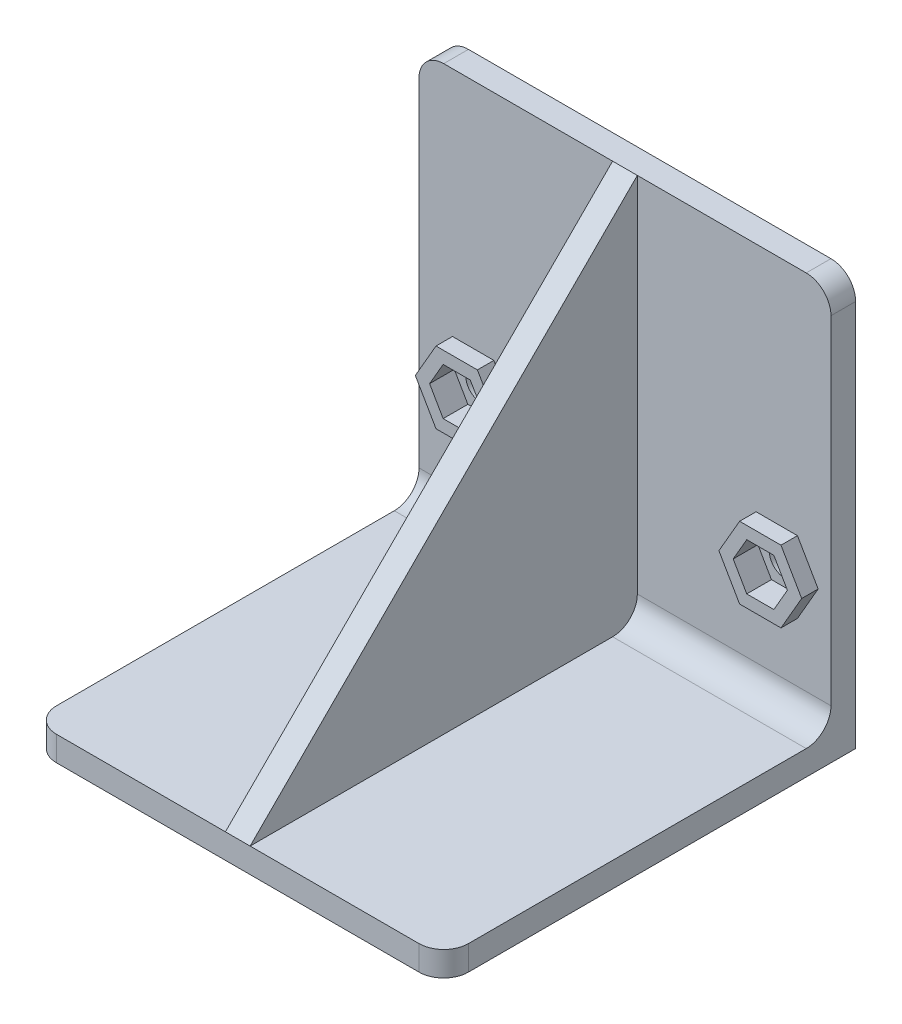
SolidWorks part; units mm, degrees
ref_plane "Front Plane" through (0, 0, 0) normal (0, 0, 1) x (1, 0, 0)
ref_plane "Top Plane" through (0, 0, 0) normal (0, 1, 0) x (1, 0, 0)
ref_plane "Right Plane" through (0, 0, 0) normal (1, 0, 0) x (0, 0, -1)
sketch "Sketch1" plane through (0, 0, 0) normal (0, 1, 0) x (1, 0, 0)
  line L1 (-25, 25) -> (25, 25)
  line L2 (-25, 25) -> (-25, -25)
  line L3 (-25, -25) -> (25, -25)
  line L4 (25, 25) -> (25, -25)
  line L5 (-25, 25) -> (25, -25) construction
  line L6 (-25, -25) -> (25, 25) construction
  point P0 (0, 0)
  dimension "D1" = 50
  dimension "D2" = 50
extrude "Boss-Extrude1" add sketch "Sketch1" along normal blind 3
sketch "Sketch2" plane through (0, 3, 0) normal (0, 1, 0) x (1, 0, 0)
  line L0 (25, -25) -> (25, 25) construction
  line L1 (-25, 25) -> (25, 25)
  line L2 (-25, 25) -> (-25, 22)
  line L3 (-25, 22) -> (25, 22)
  line L4 (25, 25) -> (25, 22)
  dimension "D1" = 3
extrude "Boss-Extrude2" add sketch "Sketch2" along normal offset from surface (47 mm away) 50 up to face at (0, 0, 0)
ref_plane "Plane1" through (0, 0, 0) normal (1, 0, 0) x (0, 0, -1)
sketch "Sketch3" plane through (0, 0, 0) normal (1, 0, 0) x (0, 0, -1)
  line L0 (-25, 3) -> (22, 50)
  line L1 (22, 50) -> (22, 3)
  line L2 (22, 3) -> (-25, 3)
extrude "Boss-Extrude3" add sketch "Sketch3" along normal mid plane 3
sketch "Sketch4" plane through (0, 0, -25) normal (0, 0, -1) x (-1, 0, 0)
  line L0 (9, 10) -> (9, 18) construction
  line L1 (13, 10) -> (5, 10)
  line L2 (13, 10) -> (13, 18)
  line L3 (13, 18) -> (5, 18)
  line L4 (5, 10) -> (5, 18)
  line L5 (25, 50) -> (25, 0) construction
  line L6 (13, 14) -> (5, 14) construction
  line L7 (-25, 0) -> (25, 0) construction
  line L8 (0, 50) -> (0, 0) construction
  line L9 (-25, 50) -> (25, 50) construction
  line L10 (-25, 17.5) -> (25, 17.5) construction
  line L11 (-25, 50) -> (-25, 0) construction
  circle A0 centre (-18.425, 17.5) radius 1.9
  circle A1 centre (18.425, 17.5) radius 1.9
  dimension "D5" = 36.85
  dimension "D6" = 3.8
  dimension "D1" = 16
  dimension "D2" = 14
  dimension "D3" = 8
  dimension "D4" = 8
  dimension "D7" = 17.5
extrude "Cut-Extrude1" cut sketch "Sketch4" against normal up to next
fillet "Fillet1" radius 1 4 edges at (-5, 10, -23.5) (-13, 10, -23.5) (-13, 18, -23.5) (-5, 18, -23.5)
sketch "Sketch5" plane through (-1.5, 0, 0) normal (-1, 0, 0) x (0, 0, 1)
  line L6 (-19, 6) -> (17.7574, 6)
  line L7 (17.7574, 6) -> (-19, 42.7574)
  line L8 (-19, 42.7574) -> (-19, 6)
  line L9 (-19, 6) -> (17.7574, 6)
  line L10 (17.7574, 6) -> (-19, 42.7574)
  line L11 (-19, 42.7574) -> (-19, 6)
  dimension "D1" = 3
sketch "Sketch6" plane through (0, 0, -22) normal (0, 0, 1) x (1, 0, 0)
  line L0 (1.5, 3) -> (25, 3) construction
  line L1 (16.7796, 14.65) -> (20.0704, 14.65)
  line L2 (20.0704, 14.65) -> (21.7159, 17.5)
  line L3 (21.7159, 17.5) -> (20.0704, 20.35)
  line L4 (20.0704, 20.35) -> (16.7796, 20.35)
  line L5 (16.7796, 20.35) -> (15.1341, 17.5)
  line L6 (15.1341, 17.5) -> (16.7796, 14.65)
  line L7 (0, 50) -> (0, 0) construction
  line L8 (1.5, 50) -> (-1.5, 50) construction
  line L9 (-20.0704, 14.65) -> (-21.7159, 17.5)
  line L10 (-21.7159, 17.5) -> (-20.0704, 20.35)
  line L11 (-20.0704, 20.35) -> (-16.7796, 20.35)
  line L12 (-16.7796, 20.35) -> (-15.1341, 17.5)
  line L13 (-15.1341, 17.5) -> (-16.7796, 14.65)
  line L14 (-16.7796, 14.65) -> (-20.0704, 14.65)
  circle A0 centre (18.425, 17.5) radius 2.85 construction
  dimension "D1" = 5.7
extrude "Cut-Extrude3" cut sketch "Sketch6" against normal blind 1
sketch "Sketch7" plane through (0, 0, -22) normal (0, 0, 1) x (1, 0, 0)
  line L48 (-15.9135, 13.15) -> (-13.4021, 17.5)
  line L49 (-20.9365, 13.15) -> (-15.9135, 13.15)
  line L50 (-23.4479, 17.5) -> (-20.9365, 13.15)
  line L51 (-20.9365, 21.85) -> (-23.4479, 17.5)
  line L52 (-15.9135, 21.85) -> (-20.9365, 21.85)
  line L53 (-13.4021, 17.5) -> (-15.9135, 21.85)
  line L54 (-15.9135, 13.15) -> (-13.4021, 17.5)
  line L55 (-20.9365, 13.15) -> (-15.9135, 13.15)
  line L56 (-23.4479, 17.5) -> (-20.9365, 13.15)
  line L57 (-20.9365, 21.85) -> (-23.4479, 17.5)
  line L58 (-15.9135, 21.85) -> (-20.9365, 21.85)
  line L59 (-13.4021, 17.5) -> (-15.9135, 21.85)
  line L66 (13.4021, 17.5) -> (15.9135, 13.15)
  line L67 (15.9135, 13.15) -> (20.9365, 13.15)
  line L68 (20.9365, 13.15) -> (23.4479, 17.5)
  line L69 (23.4479, 17.5) -> (20.9365, 21.85)
  line L70 (20.9365, 21.85) -> (15.9135, 21.85)
  line L71 (15.9135, 21.85) -> (13.4021, 17.5)
  line L72 (13.4021, 17.5) -> (15.9135, 13.15)
  line L73 (15.9135, 13.15) -> (20.9365, 13.15)
  line L74 (20.9365, 13.15) -> (23.4479, 17.5)
  line L75 (23.4479, 17.5) -> (20.9365, 21.85)
  line L76 (20.9365, 21.85) -> (15.9135, 21.85)
  line L77 (15.9135, 21.85) -> (13.4021, 17.5)
  line L79 (-16.7796, 14.65) -> (-15.1341, 17.5)
  line L80 (-20.0704, 14.65) -> (-16.7796, 14.65)
  line L81 (-21.7159, 17.5) -> (-20.0704, 14.65)
  line L82 (-20.0704, 20.35) -> (-21.7159, 17.5)
  line L83 (-16.7796, 20.35) -> (-20.0704, 20.35)
  line L84 (-15.1341, 17.5) -> (-16.7796, 20.35)
  line L85 (-16.7796, 14.65) -> (-15.1341, 17.5)
  line L86 (-20.0704, 14.65) -> (-16.7796, 14.65)
  line L87 (-21.7159, 17.5) -> (-20.0704, 14.65)
  line L88 (-20.0704, 20.35) -> (-21.7159, 17.5)
  line L89 (-16.7796, 20.35) -> (-20.0704, 20.35)
  line L90 (-15.1341, 17.5) -> (-16.7796, 20.35)
  line L92 (16.7796, 14.65) -> (20.0704, 14.65)
  line L93 (15.1341, 17.5) -> (16.7796, 14.65)
  line L94 (16.7796, 20.35) -> (15.1341, 17.5)
  line L95 (20.0704, 20.35) -> (16.7796, 20.35)
  line L96 (21.7159, 17.5) -> (20.0704, 20.35)
  line L97 (20.0704, 14.65) -> (21.7159, 17.5)
  line L98 (16.7796, 14.65) -> (20.0704, 14.65)
  line L99 (15.1341, 17.5) -> (16.7796, 14.65)
  line L100 (16.7796, 20.35) -> (15.1341, 17.5)
  line L101 (20.0704, 20.35) -> (16.7796, 20.35)
  line L102 (21.7159, 17.5) -> (20.0704, 20.35)
  line L103 (20.0704, 14.65) -> (21.7159, 17.5)
  dimension "D1" = 1.5
  dimension "D2" = 1.5
  dimension "D3" = 0
  dimension "D4" = 0
extrude "Boss-Extrude4" add sketch "Sketch7" along normal blind 2
fillet "Fillet3" radius 3 6 edges at (13.25, 3, -22) (-13.25, 3, -22) (25, 1.5, 25) (-25, 1.5, 25) (25, 50, -23.5) (-25, 50, -23.5)
